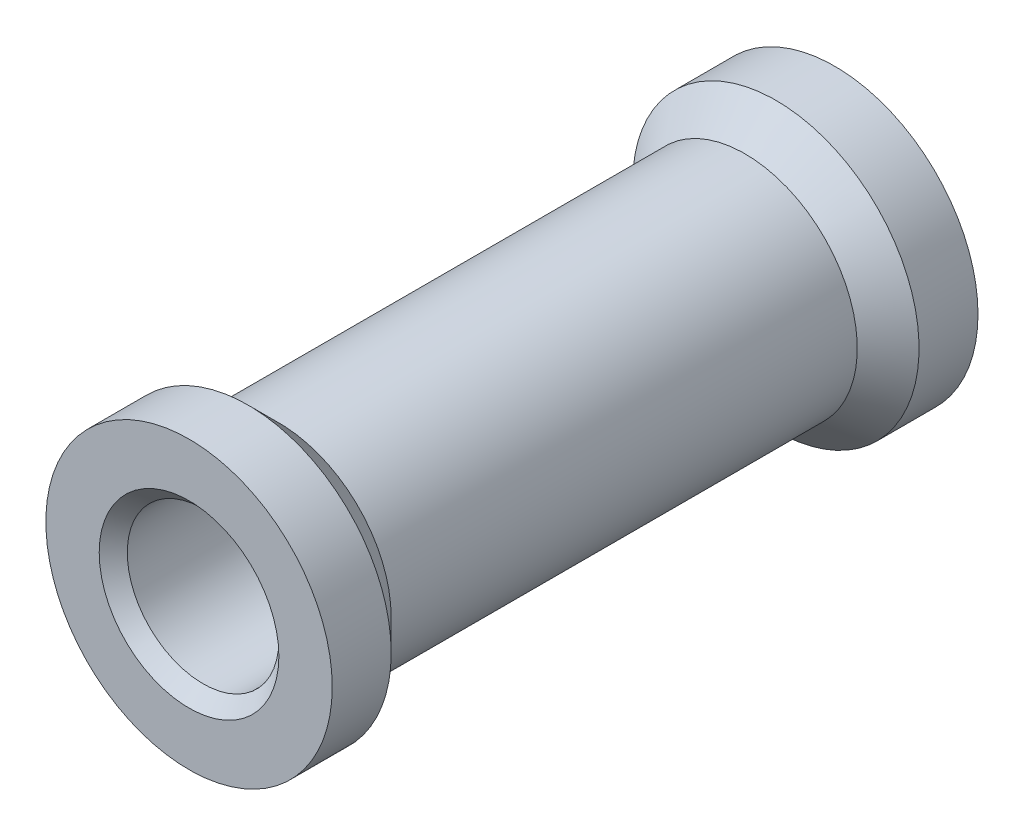
SolidWorks part; units mm, degrees
ref_plane "Front Plane" through (0, 0, 0) normal (0, 0, 1) x (1, 0, 0)
ref_plane "Top Plane" through (0, 0, 0) normal (0, 1, 0) x (1, 0, 0)
ref_plane "Right Plane" through (0, 0, 0) normal (1, 0, 0) x (0, 0, -1)
sketch "Sketch2" plane through (0, 0, 0) normal (0, 0, 1) x (1, 0, 0)
  circle A0 centre (0, 0) radius 2.7
  circle A1 centre (0, 0) radius 5.1
  dimension "D1" = 5.4
  dimension "D2" = 2.4
extrude "Boss-Extrude1" add sketch "Sketch2" along normal blind 2
sketch "Sketch3" plane through (0, 0, 2) normal (0, 0, 1) x (1, 0, 0)
  circle A0 centre (0, 0) radius 2.7
  circle A1 centre (0, 0) radius 4
  dimension "D1" = 1.3
extrude "Boss-Extrude2" add sketch "Sketch3" along normal blind 19
sketch "Sketch4" plane through (0, 0, 21) normal (0, 0, 1) x (1, 0, 0)
  circle A0 centre (0, 0) radius 5.1
  circle A1 centre (0, 0) radius 2.7
extrude "Boss-Extrude3" add sketch "Sketch4" along normal blind 2
chamfer "Chamfer1" distance 1.2 angle 45 2 edges at (4, 0, 21) (4, 0, 2)
chamfer "Chamfer2" distance 0.5 angle 45 2 edges at (2.7, 0, 0) (2.7, 0, 23)
